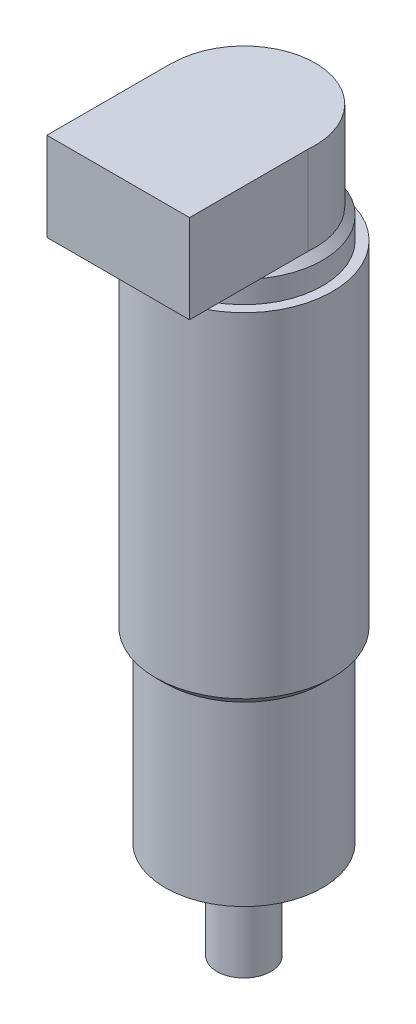
SolidWorks part; units mm, degrees
material "PUR"
ref_plane "Plan de face" through (0, 0, 0) normal (0, 0, 1) x (1, 0, 0)
ref_plane "Plan de dessus" through (0, 0, 0) normal (0, 1, 0) x (1, 0, 0)
ref_plane "Plan de droite" through (0, 0, 0) normal (1, 0, 0) x (0, 0, -1)
sketch "Esquisse1" plane through (0, 0, 0) normal (0, 1, 0) x (1, 0, 0)
  circle A0 centre (0, 0) radius 16
  dimension "D1" = 32
extrude "Boss.-Extru.1" add sketch "Esquisse1" along normal blind 36
sketch "Esquisse2" plane through (0, 36, 0) normal (0, 1, 0) x (1, 0, 0)
  circle A0 centre (0, 0) radius 18
  dimension "D1" = 36
extrude "Boss.-Extru.2" add sketch "Esquisse2" along normal blind 70
chamfer "Chanfrein1" distance 2 angle 45 1 edges at (0, 36, 18)
sketch "Esquisse3" plane through (0, 106, 0) normal (0, 1, 0) x (1, 0, 0)
  circle A0 centre (0, 0) radius 16
  dimension "D1" = 32
extrude "Boss.-Extru.3" add sketch "Esquisse3" along normal blind 6
sketch "Esquisse4" plane through (0, 112, 0) normal (0, 1, 0) x (1, 0, 0)
  circle A0 centre (0, 0) radius 14.5
  dimension "D1" = 29
extrude "Boss.-Extru.4" add sketch "Esquisse4" along normal blind 18
chamfer "Chanfrein2" distance 1.5 angle 45 1 edges at (0, 112, 16)
sketch "Esquisse5" plane through (0, 0, 0) normal (0, 0, 1) x (1, 0, 0)
  line L0 (14.5, 112) -> (-14.5, 112) construction
  line L1 (-14.5638, 130) -> (14.4362, 130)
  line L2 (-14.5638, 130) -> (-14.5638, 112)
  line L3 (-14.5638, 112) -> (14.4362, 112)
  line L4 (14.4362, 130) -> (14.4362, 112)
  line L5 (14.5, 130) -> (-14.5, 130) construction
  dimension "D1" = 0
  dimension "D2" = 0
  dimension "D3" = 29
extrude "Boss.-Extru.5" add sketch "Esquisse5" along normal blind 25.5
sketch "Esquisse6" plane through (0, 0, 0) normal (0, -1, 0) x (1, 0, 0)
  circle A0 centre (0, 0) radius 5.5
  dimension "D1" = 11
extrude "Boss.-Extru.6" add sketch "Esquisse6" along normal blind 20 contours A0
